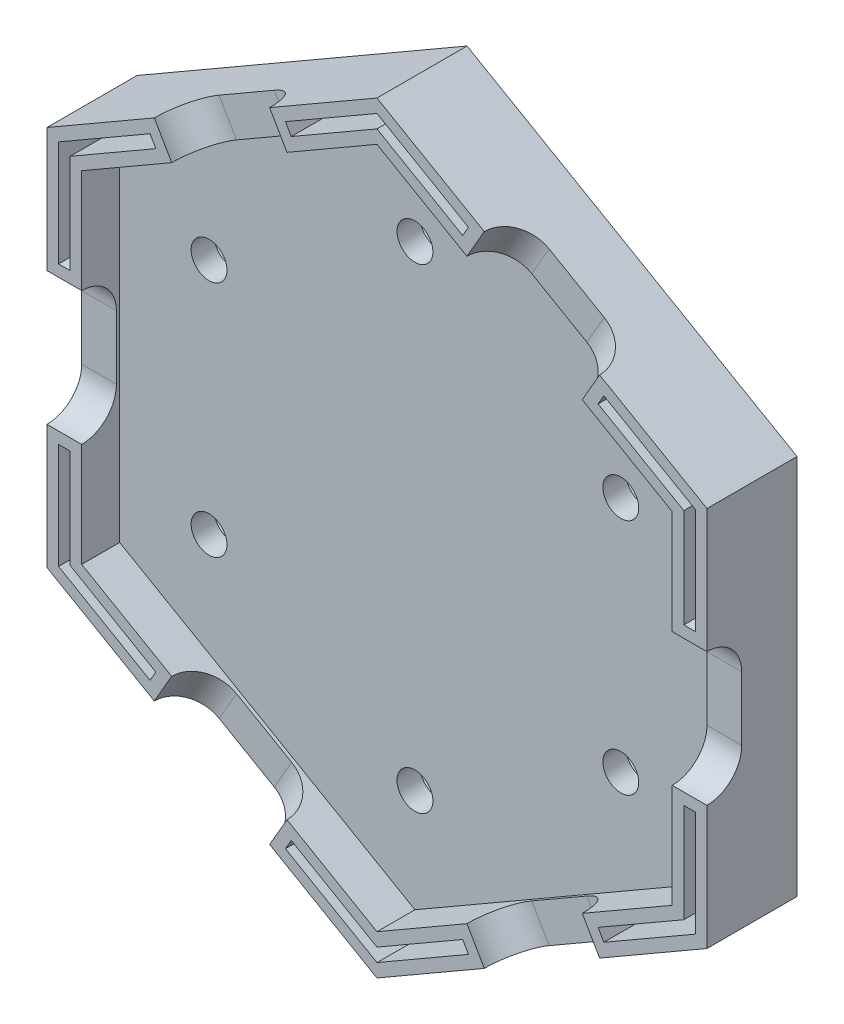
SolidWorks part; units mm, degrees
ref_plane "Front Plane" through (0, 0, 0) normal (1, 0, 0) x (0, 1, 0)
ref_plane "Top Plane" through (0, 0, 0) normal (0, 0, 1) x (0, 1, 0)
ref_plane "Right Plane" through (0, 0, 0) normal (0, 1, 0) x (-1, 0, 0)
sketch "Sketch1" plane through (0, 0, 0) normal (0, 0, 1) x (0, 1, 0)
  line L0 (0, 28.5) -> (0, -28.5) construction
  line L1 (29.4449, 0) -> (14.7224, 25.5)
  line L2 (14.7224, 25.5) -> (-14.7224, 25.5)
  line L3 (-14.7224, 25.5) -> (-29.4449, 0)
  line L4 (-29.4449, 0) -> (-14.7224, -25.5)
  line L5 (-14.7224, -25.5) -> (14.7224, -25.5)
  line L6 (14.7224, -25.5) -> (29.4449, 0)
  line L7 (32.909, 0) -> (16.4545, 28.5)
  line L8 (16.4545, 28.5) -> (-16.4545, 28.5)
  line L9 (-16.4545, 28.5) -> (-32.909, 0)
  line L10 (-32.909, 0) -> (-16.4545, -28.5)
  line L11 (-16.4545, -28.5) -> (16.4545, -28.5)
  line L12 (16.4545, -28.5) -> (32.909, 0)
  line L14 (-6.8013, 17.7802) -> (-8.5334, 20.7802)
  line L15 (-8.5334, 20.7802) -> (-11.9975, 20.7802)
  line L16 (-11.9975, 20.7802) -> (-13.7295, 17.7802)
  line L17 (-13.7295, 17.7802) -> (-11.9975, 14.7802)
  line L18 (-11.9975, 14.7802) -> (-8.5334, 14.7802)
  line L19 (-8.5334, 14.7802) -> (-6.8013, 17.7802)
  line L20 (13.7295, 17.7802) -> (11.9975, 20.7802)
  line L21 (11.9975, 20.7802) -> (8.5334, 20.7802)
  line L22 (8.5334, 20.7802) -> (6.8013, 17.7802)
  line L23 (6.8013, 17.7802) -> (8.5334, 14.7802)
  line L24 (8.5334, 14.7802) -> (11.9975, 14.7802)
  line L25 (11.9975, 14.7802) -> (13.7295, 17.7802)
  line L26 (23.9949, 0) -> (22.2629, 3)
  line L27 (22.2629, 3) -> (18.7988, 3)
  line L28 (18.7988, 3) -> (17.0667, 0)
  line L29 (17.0667, 0) -> (18.7988, -3)
  line L30 (18.7988, -3) -> (22.2629, -3)
  line L31 (22.2629, -3) -> (23.9949, 0)
  line L32 (13.7295, -17.7802) -> (11.9975, -14.7802)
  line L33 (11.9975, -14.7802) -> (8.5334, -14.7802)
  line L34 (8.5334, -14.7802) -> (6.8013, -17.7802)
  line L35 (6.8013, -17.7802) -> (8.5334, -20.7802)
  line L36 (8.5334, -20.7802) -> (11.9975, -20.7802)
  line L37 (11.9975, -20.7802) -> (13.7295, -17.7802)
  line L38 (-6.8013, -17.7802) -> (-8.5334, -14.7802)
  line L39 (-8.5334, -14.7802) -> (-11.9975, -14.7802)
  line L40 (-11.9975, -14.7802) -> (-13.7295, -17.7802)
  line L41 (-13.7295, -17.7802) -> (-11.9975, -20.7802)
  line L42 (-11.9975, -20.7802) -> (-8.5334, -20.7802)
  line L43 (-8.5334, -20.7802) -> (-6.8013, -17.7802)
  line L44 (-17.0667, 0) -> (-18.7988, 3)
  line L45 (-18.7988, 3) -> (-22.2629, 3)
  line L46 (-22.2629, 3) -> (-23.9949, 0)
  line L47 (-23.9949, 0) -> (-22.2629, -3)
  line L48 (-22.2629, -3) -> (-18.7988, -3)
  line L49 (-18.7988, -3) -> (-17.0667, 0)
  circle A0 centre (0, 0) radius 25.5 construction
  circle A1 centre (0, 0) radius 28.5 construction
  circle A2 centre (-10.2654, 17.7802) radius 1.55
  circle A3 centre (10.2654, 17.7802) radius 1.55
  circle A4 centre (20.5308, 0) radius 1.55
  circle A5 centre (10.2654, -17.7802) radius 1.55
  circle A6 centre (-10.2654, -17.7802) radius 1.55
  circle A7 centre (-20.5308, 0) radius 1.55
  circle A8 centre (-20.5308, 0) radius 7.7198 construction
  circle A9 centre (-10.2654, -17.7802) radius 7.7198 construction
  circle A10 centre (10.2654, -17.7802) radius 7.7198 construction
  circle A11 centre (20.5308, 0) radius 7.7198 construction
  circle A12 centre (10.2654, 17.7802) radius 7.7198 construction
  circle A13 centre (-10.2654, 17.7802) radius 7.7198 construction
  circle A14 centre (-10.2654, 17.7802) radius 3 construction
  circle A15 centre (10.2654, 17.7802) radius 3 construction
  circle A16 centre (20.5308, 0) radius 3 construction
  circle A17 centre (10.2654, -17.7802) radius 3 construction
  circle A18 centre (-10.2654, -17.7802) radius 3 construction
  circle A19 centre (-20.5308, 0) radius 3 construction
  dimension "D3" = 3.1
  dimension "D4" = 20.5308
  dimension "D5" = 6
  dimension "D1" = 51
  dimension "D2" = 3
extrude "Boss-Extrude1" add sketch "Sketch1" along normal blind 4.5 contours L5 L6 L1 L2 L3 L4 L49 L48 L47 L46 L45 L44 L43 L42 L41 L40 L39 L38 L37 L36 L35 L34 L33 L32 L31 L30 L29 L28 L27 L26 L25 L24 L23 L22 L21 L20 L19 L18 L17 L16 L15 L14 | L30 L31 L26 L27 L28 L29 A4 | L24 L25 L20 L21 L22 L23 A3 | L18 L19 L14 L15 L16 L17 A2 | L48 L49 L44 L45 L46 L47 A7 | L42 L43 L38 L39 L40 L41 A6 | L36 L37 L32 L33 L34 L35 A5 | L11 L12 L7 L8 L9 L10 L6 L5 L4 L3 L2 L1 region at (0, 0, 0) region at (13.8147, 23.9277, 0) region at (-16.326, -7.7467, 0) region at (-16.326, 12.7841, 0) region at (1.4542, 23.0495, 0) region at (19.2344, 12.7841, 0) region at (19.2344, -7.7467, 0) region at (1.4542, -18.0121, 0)
extrude "Cut-Extrude1" cut sketch "Sketch1<4>" along normal blind 2.5 contours L18 L19 L14 L15 L16 L17 A2 | L48 L49 L44 L45 L46 L47 A7 | L42 L43 L38 L39 L40 L41 A6 | L36 L37 L32 L33 L34 L35 A5 | L30 L31 L26 L27 L28 L29 A4 | L24 L25 L20 L21 L22 L23 A3 region at (-16.326, -7.7467, 0) region at (-16.326, 12.7841, 0) region at (1.4542, 23.0495, 0) region at (19.2344, 12.7841, 0) region at (19.2344, -7.7467, 0) region at (1.4542, -18.0121, 0)
sketch "Sketch1<4>" plane through (0, 0, 0) normal (0, 0, 1) x (0, 1, 0) same geometry as "Sketch1"
extrude "Boss-Extrude2" add sketch "Sketch1<5>" along normal blind 7.78 contours L11 L12 L7 L8 L9 L10 L6 L5 L4 L3 L2 L1 region at (13.8147, 23.9277, 0)
sketch "Sketch1<5>" plane through (0, 0, 0) normal (0, 0, 1) x (0, 1, 0) same geometry as "Sketch1"
sketch "Sketch2" plane through (-28.5, 0, 0) normal (-1, 0, 0) x (0, -1, 0)
  line L0 (-2.75, 7.78) -> (2.75, 7.78) construction
  line L1 (-16.4545, 7.78) -> (16.4545, 7.78) construction
  line L2 (-2.75, 10.78) -> (2.75, 10.78)
  line L3 (-2.75, 4.78) -> (2.75, 4.78)
  arc A0 (-2.75, 10.78) -> (-2.75, 4.78) centre (-2.75, 7.78) ccw
  arc A1 (2.75, 4.78) -> (2.75, 10.78) centre (2.75, 7.78) ccw
  point P4 (0, 7.78)
  point P9 (-5.75, 7.78)
  point P10 (5.75, 7.78)
  dimension "D1" = 11.5
  dimension "D2" = 6
extrude "Cut-Extrude2" cut sketch "Sketch2" against normal up to surface (57 mm away) up to face at (28.5, 0, 3.89)
sketch "Sketch3" plane through (-14.25, -24.6817, 0) normal (-0.5, -0.866, 0) x (0.866, -0.5, 0)
  line L0 (-2.75, 7.78) -> (2.75, 7.78) construction
  line L1 (-2.75, 10.78) -> (2.75, 10.78)
  line L2 (-2.75, 4.78) -> (2.75, 4.78)
  line L3 (-16.4545, 7.78) -> (16.4545, 7.78) construction
  arc A0 (-2.75, 10.78) -> (-2.75, 4.78) centre (-2.75, 7.78) ccw
  arc A1 (2.75, 4.78) -> (2.75, 10.78) centre (2.75, 7.78) ccw
  point P2 (0, 7.78)
  point P7 (-5.75, 7.78)
  point P8 (5.75, 7.78)
  dimension "D1" = 11.5
  dimension "D2" = 6
extrude "Cut-Extrude3" cut sketch "Sketch3" against normal up to surface (57 mm away) up to face at (14.25, 24.6817, 3.89)
sketch "Sketch4" plane through (14.25, -24.6817, 0) normal (0.5, -0.866, 0) x (0.866, 0.5, 0)
  line L0 (-2.75, 7.78) -> (2.75, 7.78) construction
  line L1 (-2.75, 10.78) -> (2.75, 10.78)
  line L2 (-2.75, 4.78) -> (2.75, 4.78)
  line L3 (-16.4545, 7.78) -> (16.4545, 7.78) construction
  arc A0 (-2.75, 10.78) -> (-2.75, 4.78) centre (-2.75, 7.78) ccw
  arc A1 (2.75, 4.78) -> (2.75, 10.78) centre (2.75, 7.78) ccw
  point P2 (0, 7.78)
  point P7 (-5.75, 7.78)
  point P8 (5.75, 7.78)
  dimension "D1" = 11.5
  dimension "D2" = 6
extrude "Cut-Extrude4" cut sketch "Sketch4" against normal up to surface (57 mm away) up to face at (-14.25, 24.6817, 3.89)
sketch "Sketch7" plane through (0, 0, 7.78) normal (0, 0, 1) x (1, 0, 0)
  line L0 (-19.2296, 21.8067) -> (-17.7296, 19.2086) construction
  line L1 (-26.5, -6.75) -> (-26.5, -15.2998)
  line L2 (-19.0957, -19.5747) -> (-26.5, -15.2998)
  line L3 (-27.5, 6.75) -> (-26.5, 6.75)
  line L4 (-27.5, 6.75) -> (-27.5, 15.8771)
  line L6 (-26.5, 6.75) -> (-26.5, 15.2998)
  line L7 (-28.5, 16.4545) -> (-25.5, 14.7224) construction
  line L8 (-19.5957, -20.4407) -> (-19.0957, -19.5747)
  line L13 (-19.5957, -20.4407) -> (-27.5, -15.8771)
  line L14 (-27.5, -6.75) -> (-27.5, -15.8771)
  line L19 (-27.5, -6.75) -> (-26.5, -6.75)
  line L20 (-7.4043, -26.3247) -> (0, -30.5996)
  line L25 (7.4043, -26.3247) -> (0, -30.5996)
  line L26 (7.9043, -27.1907) -> (7.4043, -26.3247)
  line L27 (-19.5957, 20.4407) -> (-27.5, 15.8771)
  line L28 (-19.5957, 20.4407) -> (-19.0957, 19.5747)
  line L30 (-19.0957, 19.5747) -> (-26.5, 15.2998)
  line L31 (7.9043, -27.1907) -> (0, -31.7543)
  line L32 (-7.9043, -27.1907) -> (0, -31.7543)
  line L33 (-7.9043, -27.1907) -> (-7.4043, -26.3247)
  line L34 (19.0957, -19.5747) -> (26.5, -15.2998)
  line L35 (26.5, -6.75) -> (26.5, -15.2998)
  line L36 (27.5, -6.75) -> (26.5, -6.75)
  line L37 (27.5, -6.75) -> (27.5, -15.8771)
  line L38 (19.5957, -20.4407) -> (27.5, -15.8771)
  line L39 (19.5957, -20.4407) -> (19.0957, -19.5747)
  line L40 (26.5, 6.75) -> (26.5, 15.2998)
  line L41 (19.0957, 19.5747) -> (26.5, 15.2998)
  line L42 (19.5957, 20.4407) -> (19.0957, 19.5747)
  line L43 (19.5957, 20.4407) -> (27.5, 15.8771)
  line L44 (27.5, 6.75) -> (27.5, 15.8771)
  line L45 (27.5, 6.75) -> (26.5, 6.75)
  line L46 (7.4043, 26.3247) -> (0, 30.5996)
  line L47 (-7.4043, 26.3247) -> (0, 30.5996)
  line L48 (-7.9043, 27.1907) -> (-7.4043, 26.3247)
  line L49 (-7.9043, 27.1907) -> (0, 31.7543)
  line L50 (7.9043, 27.1907) -> (0, 31.7543)
  line L51 (7.9043, 27.1907) -> (7.4043, 26.3247)
  line L54 (-25.5, -14.7224) -> (-25.5, 14.7224) construction
  point P46 (0, 0)
  dimension "D1" = 1
  dimension "D2" = 1
  dimension "D3" = 120
  dimension "D4" = 1
  dimension "D5" = 6
extrude "Cut-Extrude5" cut sketch "Sketch7" against normal blind 5
